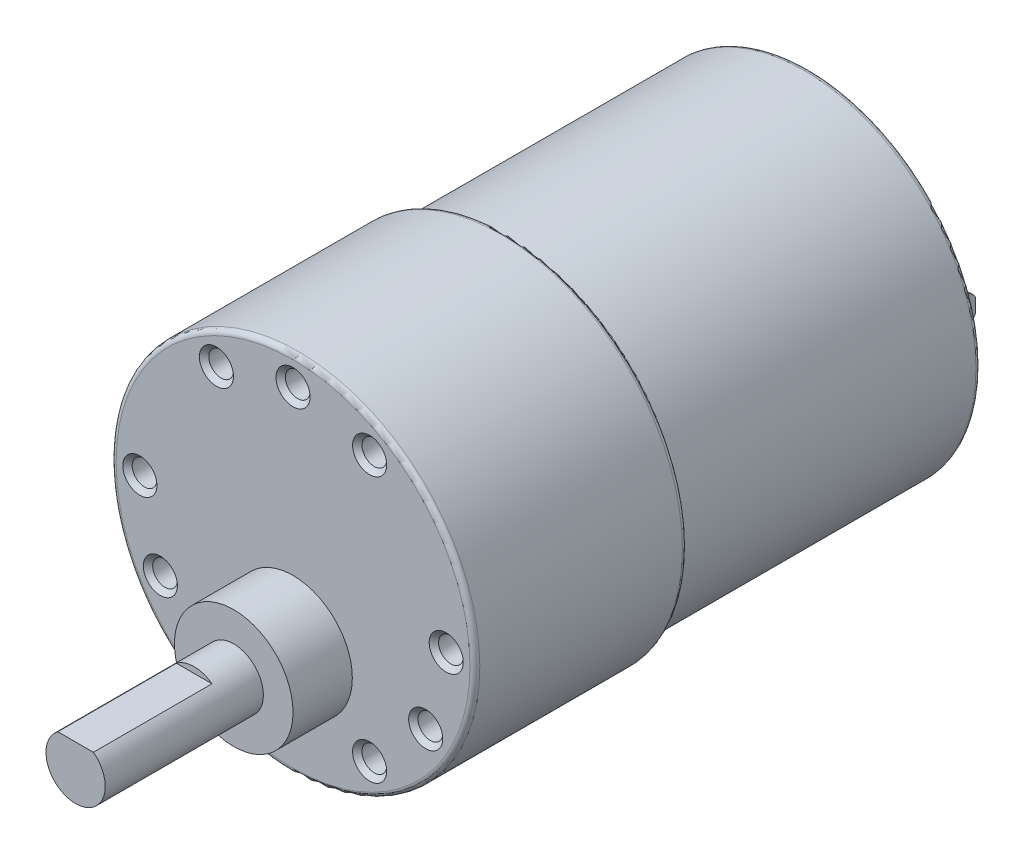
SolidWorks part; units mm, degrees
ref_plane "Front Plane" through (0, 0, 0) normal (0, 0, 1) x (1, 0, 0)
ref_plane "Top Plane" through (0, 0, 0) normal (0, 1, 0) x (1, 0, 0)
ref_plane "Right Plane" through (0, 0, 0) normal (1, 0, 0) x (0, 0, -1)
sketch "Sketch1" plane through (0, 0, 0) normal (0, 0, 1) x (1, 0, 0)
  circle A0 centre (0, 0) radius 18.4
  dimension "D1" = 36.8
extrude "gear box" add sketch "Sketch1" along normal blind 21.5
sketch "Sketch2" plane through (0, 0, 0) normal (0, 0, -1) x (-1, 0, 0)
  circle A0 centre (0, 0) radius 17.4
  dimension "D1" = 34.8
extrude "motor coils" add sketch "Sketch2" along normal blind 30.7
sketch "Sketch3" plane through (0, 0, -30.7) normal (0, 0, -1) x (-1, 0, 0)
  line L0 (0, 20.24) -> (0, -20.24) construction
  circle A0 centre (-11.6123, 0) radius 1.55
  circle A1 centre (11.6123, 0) radius 1.55
  dimension "D1" = 3.1
  dimension "D2" = 11.6123
extrude "Boss-Extrude3" add sketch "Sketch3" along normal blind 0.5
sketch "Sketch4" plane through (0, 0, -31.2) normal (0, 0, -1) x (-1, 0, 0)
  line L1 (-11.8623, 1.45) -> (-11.3623, 1.45)
  line L2 (-11.8623, 1.45) -> (-11.8623, -1.45)
  line L3 (-11.8623, -1.45) -> (-11.3623, -1.45)
  line L4 (-11.3623, 1.45) -> (-11.3623, -1.45)
  line L5 (-11.8623, 1.45) -> (-11.3623, -1.45) construction
  line L6 (-11.8623, -1.45) -> (-11.3623, 1.45) construction
  point P0 (-11.6123, 0)
  dimension "D1" = 0.5
  dimension "D2" = 2.9
extrude "Boss-Extrude4" add sketch "Sketch4" along normal blind 4.5
mirror "Mirror1" about plane through (0, 0, 0) normal (1, 0, 0) of "Boss-Extrude4"
sketch "Sketch6" plane through (11.8623, 0, 0) normal (1, 0, 0) x (0, 0, -1)
  line L0 (32.167, 0) -> (34.6761, 0) construction
  line L1 (20.24, 0) -> (-20.24, 0) construction
  line L2 (32.167, 0.592) -> (34.6761, 0.592)
  line L3 (32.167, -0.592) -> (34.6761, -0.592)
  line L4 (35.7, 1.45) -> (31.2, 1.45) construction
  line L5 (35.7, 1.45) -> (35.7, -1.45) construction
  line L6 (34.7902, 1.45) -> (35.8546, 1.9485)
  line L7 (35.8546, 1.9485) -> (37.86, 0.483)
  line L8 (37.86, 0.483) -> (37.5052, -1.3065)
  line L9 (37.5052, -1.3065) -> (35.1758, -1.8773)
  line L10 (35.1758, -1.8773) -> (34.7902, -1.45)
  line L11 (35.7, -0.6989) -> (35.7, 0.6989)
  arc A0 (32.167, 0.592) -> (32.167, -0.592) centre (32.167, 0) ccw
  arc A1 (34.6761, -0.592) -> (34.6761, 0.592) centre (34.6761, 0) ccw
  spline S0 degree 2 poles (34.7902, 1.45) (35.4004, 1.2613) (35.7, 0.6989) knots 0 0 0 1 1 1
  spline S1 degree 2 poles (34.7902, -1.45) (35.4004, -1.2613) (35.7, -0.6989) knots 0 0 0 1 1 1
  point P5 (33.4215, 0)
extrude "Cut-Extrude1" cut sketch "Sketch6" against normal through all
sketch "Sketch7" plane through (0, 0, -30.7) normal (0, 0, -1) x (-1, 0, 0)
  circle A0 centre (0, 0) radius 3.9
  dimension "D1" = 7.8
extrude "Boss-Extrude5" add sketch "Sketch7" along normal blind 1.6
sketch "Sketch8" plane through (0, 0, 21.5) normal (0, 0, 1) x (1, 0, 0)
  circle A0 centre (0, -7) radius 6
  dimension "D2" = 12
  dimension "D1" = 7
extrude "Boss-Extrude6" add sketch "Sketch8" along normal blind 6
sketch "Sketch9" plane through (0, 0, 27.5) normal (0, 0, 1) x (1, 0, 0)
  circle A0 centre (0, -7) radius 3
  dimension "D1" = 6
extrude "Boss-Extrude7" add sketch "Sketch9" along normal blind 16
sketch "Sketch10" plane through (0, 0, 43.5) normal (0, 0, 1) x (1, 0, 0)
  line L0 (-1.8, -4.6) -> (1.8, -4.6)
  line L1 (0, -10) -> (3, -10) construction
  circle A1 centre (0, -7) radius 3
  arc A2 (1.8, -4.6) -> (-1.8, -4.6) centre (0, -7) ccw
  dimension "D2" = 5.4
  dimension "D1" = 0
extrude "Cut-Extrude2" cut sketch "Sketch10" against normal blind 12
hole_wizard "M3 Tapped Hole1" positions "3DSketch1" profile "Sketch11" tap size "M3" standard "AS"
sketch3d "3DSketch1"
  line L9 (0, 0, 21.5) -> (0, 10.082, 21.5) construction
  line L10 (-7.75, 13.4234, 21.5) -> (7.75, 13.4234, 21.5)
  line L12 (0, 0, 21.5) -> (7.5161, 0, 21.5) construction
  line L15 (-7.75, 13.4234, 21.5) -> (7.75, 13.4234, 21.5)
  line L16 (-7.75, 13.4234, 21.5) -> (-7.75, -13.4234, 21.5)
  line L17 (-7.75, -13.4234, 21.5) -> (7.75, -13.4234, 21.5)
  line L18 (7.75, 13.4234, 21.5) -> (7.75, -13.4234, 21.5)
  circle A1 centre (0, 0, 21.5) radius 15.5
  point P103 (-7.75, 13.4234, 21.5)
  point P107 (7.75, 13.4234, 21.5)
  point P113 (0, 13.4234, 21.5)
  point P911 (7.75, 0, 21.5)
  point P932 (0, 15.5, 21.5)
  point P951 (0, 0, 37)
  point P954 (0, 0, 0)
  point P955 (0, 0, 0)
  point P956 (0, 0, 0)
  point P957 (0, 0, 0)
  point P958 (0, 0, 0)
  dimension "D1" = 15.5
  dimension "D2" = 31
sketch "Sketch11" plane through (0, 15.5, 21.5) normal (1, 0, 0) x (0, -1, 0)
  line L0 (0, 0) -> (0, 5)
  line L1 (0, 5) -> (1.25, 4.2489)
  line L2 (1.25, 4.2489) -> (1.25, 0.475)
  line L3 (1.25, 0.475) -> (1.725, 0)
  line L5 (1.725, 0) -> (0, 0)
  line L6 (-1.25, 0.475) -> (-1.725, 0) construction
  line L10 (0, 5) -> (-1.25, 4.2489) construction
  line L11 (0, -6.35) -> (0, 107.95) construction
  dimension "Tap Drill Dia." = 2.5
  dimension "Tap Drill Depth" = 5
  dimension "Near C'Sink Dia." = 3.45
  dimension "Near C'Sink Angle" = 90
  dimension "Drill Angle" = 118
cosmetic thread "Hole Thread44" parameters "D1"=6, "D2"=3
cosmetic thread "Hole Thread47" parameters "D1"=6, "D2"=3
cosmetic thread "Hole Thread48" parameters "D1"=6, "D2"=3
pattern_circular "CirPattern1" count 3 over 360 about axis through (0, 0, 21.5) along (0, 0, -1) of "M3 Tapped Hole1"
cosmetic thread "Hole Thread49" parameters "D1"=6, "D2"=3
cosmetic thread "Hole Thread50" parameters "D1"=6, "D2"=3
cosmetic thread "Hole Thread51" parameters "D1"=6, "D2"=3
cosmetic thread "Hole Thread52" parameters "D1"=6, "D2"=3
cosmetic thread "Hole Thread53" parameters "D1"=6, "D2"=3
cosmetic thread "Hole Thread54" parameters "D1"=6, "D2"=3
fillet "Fillet1" radius 0.5 4 edges at (18.4, 0, 0) (18.4, 0, 21.5) (-17.4, 0, 0) (-17.4, 0, -30.7)
